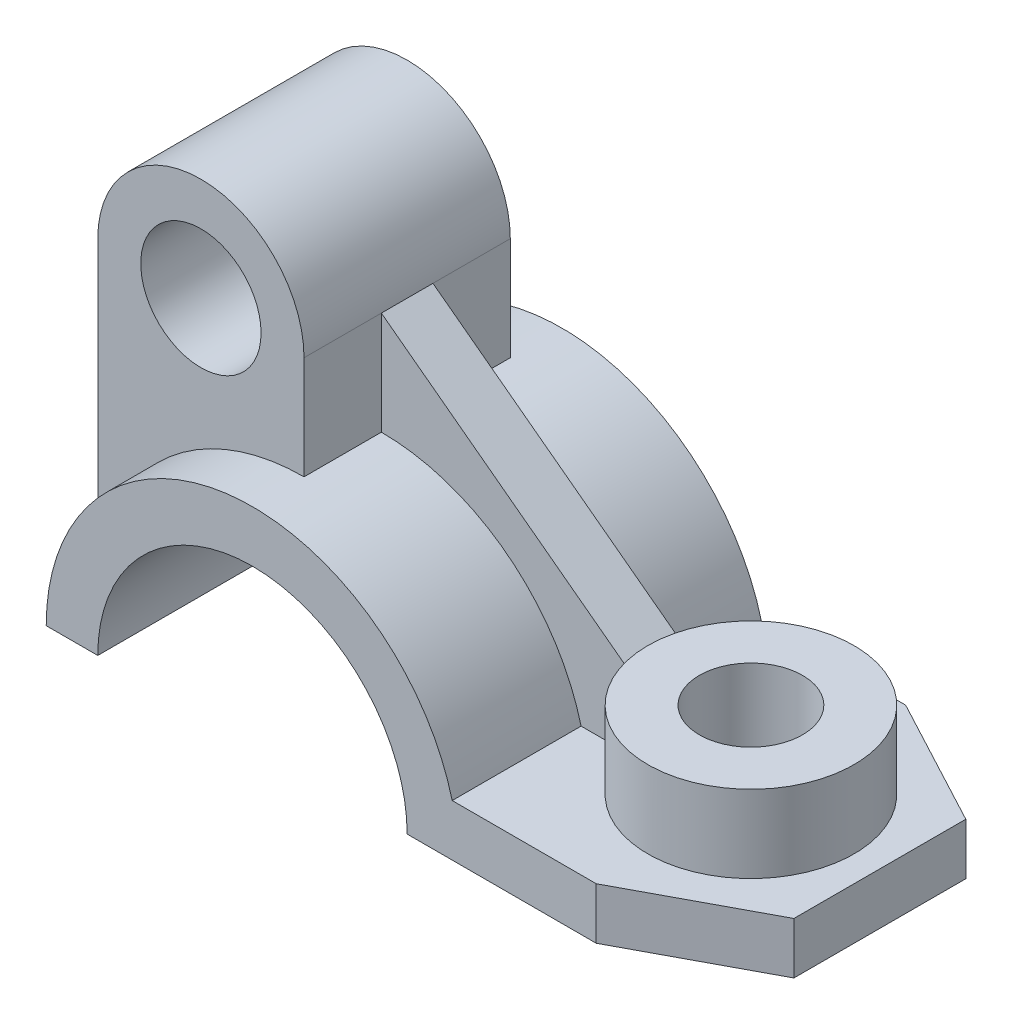
SolidWorks part; units mm, degrees
ref_plane "Front Plane" through (0, 0, 0) normal (0, 0, 1) x (1, 0, 0)
ref_plane "Top Plane" through (0, 0, 0) normal (0, 1, 0) x (1, 0, 0)
ref_plane "Right Plane" through (0, 0, 0) normal (1, 0, 0) x (0, 0, -1)
sketch "Sketch1" plane through (0, 0, 0) normal (0, 0, 1) x (1, 0, 0)
  line L0 (-24, 0) -> (-24, 36)
  line L1 (0, 36) -> (0, 24)
  line L2 (-24, 0) -> (-18, 0)
  line L3 (18, 0) -> (24, 0)
  line L4 (24, 0) -> (55, 0)
  line L5 (55, 0) -> (55, 6)
  line L6 (55, 6) -> (23.2379, 6)
  arc A0 (-18, 0) -> (18, 0) centre (0, 0) cw
  arc A1 (24, 0) -> (-24, 0) centre (0, 0) ccw
  arc A2 (-24, 36) -> (0, 36) centre (-12, 36) cw
  circle A3 centre (-12, 36) radius 7
  point P14 (0, 0)
  dimension "D1" = 24
  dimension "D2" = 18
  dimension "D3" = 36
  dimension "D4" = 12
  dimension "D5" = 14
  dimension "D6" = 55
  dimension "D7" = 6
extrude "Boss-Extrude1" add sketch "Sketch1" along normal mid plane 36 contours L3 A1 L2 A0 | A1 L4 L5 L6 region at (-16.5911, 16.5911, 0) region at (39.373, 3.0122, 0)
extrude "Boss-Extrude2" add sketch "Sketch1<3>" along normal mid plane 24 contours A2 L0 A1 L1 A3 region at (-23.4633, 18, 0)
sketch "Sketch1<3>" plane through (0, 0, 0) normal (0, 0, 1) x (1, 0, 0) same geometry as "Sketch1"
sketch "Sketch2" plane through (0, 6, 0) normal (0, 1, 0) x (1, 0, 0)
  line L0 (0, -12) -> (0, 12) construction
  circle A0 centre (40, 0) radius 12
  circle A1 centre (40, 0) radius 6
  point P3 (40, 0)
  point P7 (0, 0)
  point P8 (40, 0)
  dimension "D1" = 24
  dimension "D2" = 12
  dimension "D3" = 40
extrude "Boss-Extrude3" add sketch "Sketch2" along normal blind 9
sketch "Sketch3" plane through (0, 0, 0) normal (0, 0, 1) x (1, 0, 0)
  line L0 (0, 36) -> (28, 15)
rib "Rib1" sketch "Sketch3" sketch "Sketch3" thickness 6 extrusion direction parallel to sketch draft on no parameters "D1"=6
chamfer "Chamfer1" distance 8 distance2 15 1 edges at (55, 3, 18) first distance on face at (55, 3, 0)
chamfer "Chamfer2" distance 15 distance2 8 1 edges at (55, 3, -18) first distance on face at (17.7658, 8.4681, -18)
extrude "Cut-Extrude1" cut sketch "Sketch2<2>" against normal through all contours A1 region at (40, 6, 0)
sketch "Sketch2<2>" plane through (0, 6, 0) normal (0, 1, 0) x (1, 0, 0) same geometry as "Sketch2"
